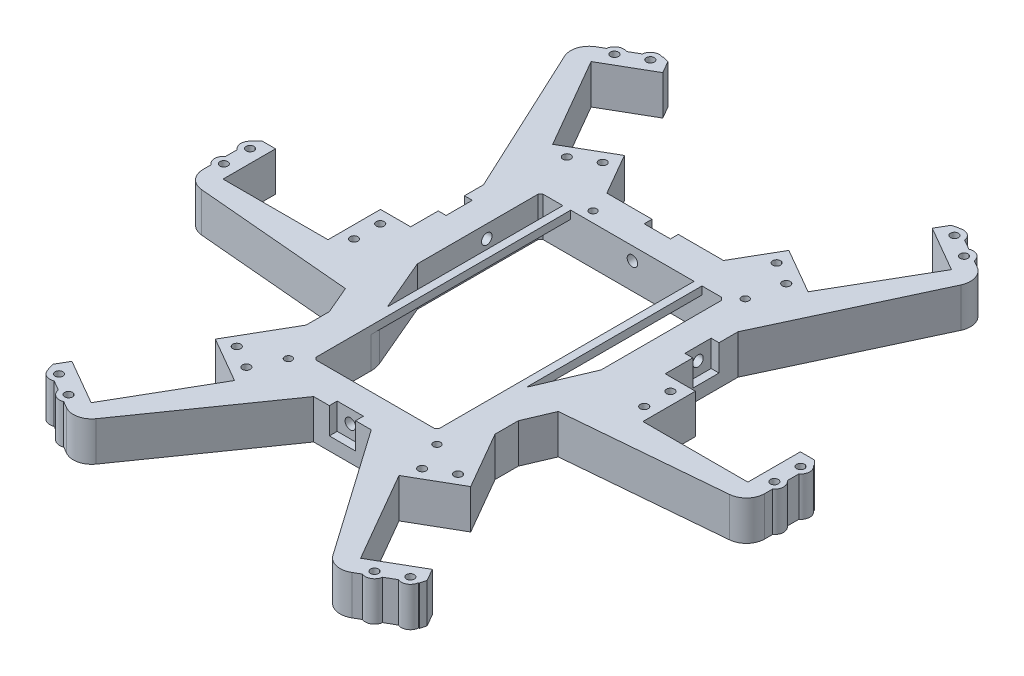
SolidWorks part; units mm, degrees
material "PETG"
ref_plane "Front Plane" through (0, 0, 0) normal (0, 0, 1) x (1, 0, 0)
ref_plane "Top Plane" through (0, 0, 0) normal (0, 1, 0) x (1, 0, 0)
ref_plane "Right Plane" through (0, 0, 0) normal (1, 0, 0) x (0, 0, -1)
sketch "Sketch1" plane through (0, 0, 0) normal (0, 1, 0) x (1, 0, 0)
  line L0 (-42.2601, -28.5633) -> (-31.2399, -54.4367)
  line L1 (-42.5, -28) -> (42.5, -28) construction
  line L2 (-42.5, -27.3877) -> (-42.5, 25)
  line L3 (-39.5, 28) -> (39.5, 28)
  line L4 (42.5, -27.3877) -> (42.5, 25)
  line L5 (-42.5, -28) -> (42.5, 28) construction
  line L6 (-42.5, 28) -> (42.5, -28) construction
  line L7 (-30, -85) -> (30, -85)
  line L8 (-31, -85) -> (-31, -43) construction
  line L9 (-31, -43) -> (31, -43) construction
  line L10 (31, -85) -> (31, -43) construction
  line L11 (-31, -85) -> (31, -43) construction
  line L12 (-31, -43) -> (31, -85) construction
  line L13 (-31, -55.6123) -> (-31, -84)
  line L14 (42.2601, -28.5633) -> (31.2399, -54.4367)
  line L15 (31, -55.6123) -> (31, -84)
  arc A0 (39.5, 28) -> (42.5, 25) centre (39.5, 25) cw
  arc A1 (-42.5, 25) -> (-39.5, 28) centre (-39.5, 25) cw
  arc A2 (-30, -85) -> (-31, -84) centre (-30, -84) cw
  arc A3 (30, -85) -> (31, -84) centre (30, -84) ccw
  arc A4 (-31.2399, -54.4367) -> (-31, -55.6123) centre (-34, -55.6123) cw
  arc A5 (31.2399, -54.4367) -> (31, -55.6123) centre (34, -55.6123) ccw
  arc A6 (42.2601, -28.5633) -> (42.5, -27.3877) centre (39.5, -27.3877) ccw
  arc A7 (-42.2601, -28.5633) -> (-42.5, -27.3877) centre (-39.5, -27.3877) cw
  point P0 (0, 0)
  point P12 (0, -64)
  point P31 (-31, -55)
  point P34 (31, -55)
  dimension "D3" = 3
  dimension "D8" = 1
  dimension "D9" = 3
  dimension "D1" = 85
  dimension "D2" = 56
  dimension "D4" = 62
  dimension "D5" = 42
  dimension "D6" = 15
  dimension "D7" = 30
extrude "Boss-Extrude1" add sketch "Sketch1" along normal blind 4
sketch "Sketch2" plane through (0, 4, 0) normal (0, 1, 0) x (1, 0, 0)
  line L0 (39.5, 28) -> (-39.5, 28) construction
  line L1 (42.5, -27.3877) -> (42.5, 25) construction
  line L2 (-31, -55.6123) -> (-31, -84) construction
  line L3 (-30, -85) -> (30, -85) construction
  line L5 (31, -84) -> (31, -55.6123) construction
  circle A0 centre (39, 24.5) radius 1.4
  circle A1 centre (-19, 24.5) radius 1.4
  circle A2 centre (-19, -24.5) radius 1.4
  circle A3 centre (39, -24.5) radius 1.4
  circle A4 centre (-28.3, -82.3) radius 1.4
  circle A5 centre (-28.3, -45.7) radius 1.4
  circle A6 centre (28.3, -45.7) radius 1.4
  circle A7 centre (28.3, -82.3) radius 1.4
  dimension "D3" = 2.8
  dimension "D4" = 2.8
  dimension "D5" = 2.8
  dimension "D6" = 2.8
  dimension "D9" = 2.8
  dimension "D14" = 2.8
  dimension "D15" = 2.8
  dimension "D16" = 2.8
  dimension "D12" = 2.7
  dimension "D1" = 3.5
  dimension "D2" = 3.5
  dimension "D7" = 49
  dimension "D8" = 58
  dimension "D10" = 2.7
  dimension "D11" = 2.7
  dimension "D13" = 36.6
sketch "Sketch11" plane through (0, 0, 0) normal (0, 1, 0) x (1, 0, 0)
  line L0 (0, -25.5) -> (-55, 69.7628) construction
  line L1 (0, -25.5) -> (-90, -25.5) construction
  line L2 (0, -25.5) -> (-55, -120.7628) construction
  line L3 (0, -25.5) -> (55, 69.7628) construction
  line L4 (0, -25.5) -> (90, -25.5) construction
  line L5 (0, -25.5) -> (55, -120.7628) construction
  line L6 (0, -18.7219) -> (0, 33) construction
  line L7 (48.6603, 38.782) -> (31.3397, 48.782)
  line L9 (41.7138, 26.7504) -> (25041.7138, 43328.0205) construction
  line L10 (24.3933, 36.7504) -> (25024.3933, 43338.0205) construction
  line L11 (48.6603, 38.782) -> (68.6603, 73.423)
  line L12 (68.6603, 73.423) -> (51.3397, 83.423)
  line L13 (51.3397, 83.423) -> (54.8397, 89.4852)
  line L14 (54.8397, 89.4852) -> (78.2224, 75.9852)
  line L16 (48.5, 12.2453) -> (48.5, -15.5)
  line L17 (60, -35.5) -> (100, -35.5)
  line L18 (100, -35.5) -> (100, -15.5)
  line L19 (100, -15.5) -> (107, -15.5)
  line L20 (107, -15.5) -> (107, -42.5)
  line L23 (41.5211, -131.4167) -> (-24958.4789, 43169.8535) construction
  line L24 (31.2399, -54.4367) -> (42.2601, -28.5633) construction
  line L32 (39, 33) -> (0, 33) construction
  line L33 (-48.5, 25) -> (-48.5, 24.5045) construction
  line L36 (0, -90) -> (28.3, -90) construction
  line L37 (36, -82.3) -> (36, -59) construction
  line L38 (36, -59) -> (46.7802, -33.6899) construction
  line L40 (35, 20.5) -> (-35, 20.5)
  line L41 (-35, 20.5) -> (-35, -26.4693)
  line L42 (-35, -26.4693) -> (-24.3397, -51.4977)
  line L43 (-23.5, -55.6123) -> (-23.5, -77.5)
  line L44 (-23.5, -77.5) -> (23.5, -77.5)
  line L45 (23.5, -77.5) -> (23.5, -55.6123)
  line L46 (24.3397, -51.4977) -> (35, -26.4693)
  line L47 (35, -26.4693) -> (35, 20.5)
  line L48 (35, 20.5) -> (-35, 20.5) construction
  line L49 (-35, 20.5) -> (-35, -26.4693) construction
  line L50 (-35, -26.4693) -> (-24.3397, -51.4977) construction
  line L51 (-23.5, -55.6123) -> (-23.5, -77.5) construction
  line L52 (-23.5, -77.5) -> (23.5, -77.5) construction
  line L53 (23.5, -77.5) -> (23.5, -55.6123) construction
  line L54 (24.3397, -51.4977) -> (35, -26.4693) construction
  line L55 (35, -26.4693) -> (35, 20.5) construction
  line L57 (48.7776, -143.9852) -> (72.1603, -130.4852)
  line L58 (72.1603, -130.4852) -> (68.6603, -124.423)
  line L59 (68.6603, -124.423) -> (51.3397, -134.423)
  line L60 (51.3397, -134.423) -> (31.3397, -99.782)
  line L61 (31.3397, -99.782) -> (48.6603, -89.782)
  line L63 (0, -90) -> (0, -77.5)
  line L64 (0, -77.5) -> (23.5, -77.5)
  line L65 (23.5, -77.5) -> (23.5, -55.6123)
  line L66 (0, 33) -> (0, 20.5)
  line L67 (0, 20.5) -> (35, 20.5)
  line L68 (35, 20.5) -> (35, -26.4693)
  line L69 (35, -26.4693) -> (24.3397, -51.4977)
  line L72 (40.5517, -48.3135) -> (107, -42.5)
  line L73 (78.2224, 75.9852) -> (-24921.7776, -43225.285) construction
  line L74 (78.2224, 75.9852) -> (48.5, 12.2453)
  line L75 (107, -42.5) -> (50107, -42.5) construction
  line L76 (48.7776, -143.9852) -> (10.9767, -90)
  line L82 (0, 44.3223) -> (0, 49981.2781) construction
  line L83 (31.3397, 48.782) -> (22.228, 33)
  line L84 (22.228, 33) -> (0, 33)
  line L85 (40.5517, -48.3135) -> (36, -59)
  line L86 (36, -59) -> (36, -67.8538)
  line L87 (36, -67.8538) -> (48.6603, -89.782)
  line L88 (10.9767, -90) -> (0, -90)
  line L89 (48.5, -15.5) -> (60, -15.5)
  line L90 (60, -15.5) -> (60, -35.5)
  line L92 (48.5, -15.5) -> (48.5, 12.2453) construction
  circle A0 centre (-28.3, -82.3) radius 1.4 construction
  circle A2 centre (-19, 24.5) radius 1.4 construction
  circle A4 centre (-28.3, -82.3) radius 1.4 construction
  circle A6 centre (-19, 24.5) radius 1.4 construction
  arc A22 (48.5, 23.5) -> (39, 33) centre (39, 23.5) ccw construction
  arc A26 (28.3, -90) -> (36, -82.3) centre (28.3, -82.3) ccw construction
  arc A27 (46.7802, -33.6899) -> (47.5, -30.1632) centre (38.5, -30.1632) ccw construction
  arc A28 (-23.5, -55.6123) -> (-24.3397, -51.4977) centre (-34, -55.6123) ccw
  arc A29 (24.3397, -51.4977) -> (23.5, -55.6123) centre (34, -55.6123) ccw
  arc A30 (-23.5, -55.6123) -> (-24.3397, -51.4977) centre (-34, -55.6123) ccw construction
  arc A31 (24.3397, -51.4977) -> (23.5, -55.6123) centre (34, -55.6123) ccw
  point P0 (0, -25.5)
  point P4 (33.775, 33)
  point P17 (-35.9261, -87.7258)
  point P27 (52.5, -25.5)
  point P28 (34.9923, -86.1084)
  point P30 (40, 43.782)
  point P31 (-33.775, 33)
  point P69 (34.9923, -86.1084)
  dimension "D28" = 40
  dimension "D1" = 60
  dimension "D2" = 60
  dimension "D3" = 60
  dimension "D4" = 33
  dimension "D6" = 46
  dimension "D7" = 5
  dimension "D8" = 5
  dimension "D9" = 40
  dimension "D10" = 7
  dimension "D11" = 27
  dimension "D12" = 20
  dimension "D13" = 10
  dimension "D14" = 10
  dimension "D15" = 7
  dimension "D16" = 10
  dimension "D17" = 7
  dimension "D18" = 10
  dimension "D19" = 14
  dimension "D20" = 7
  dimension "D21" = 10
  dimension "D22" = 40
  dimension "D23" = 5
  dimension "D24" = 10
  dimension "D25" = 110
  dimension "D26" = 90
  dimension "D27" = 10
  dimension "D29" = 25.5
  dimension "D30" = 48.5
  dimension "D31" = 36
  dimension "D32" = 64.5
  dimension "D33" = 31
  dimension "D5" = 7.5
extrude "Boss-Extrude4" add sketch "Sketch11" against normal blind 15
mirror "Mirror1" about plane through (0, 0, 0) normal (1, 0, 0) of "Boss-Extrude4"
sketch "Sketch14" plane through (0, 0, 0) normal (0, 1, 0) x (1, 0, 0)
  line L8 (39.5, 28) -> (-39.5, 28)
  line L9 (-42.5, 25) -> (-42.5, -27.3877)
  line L10 (-42.2601, -28.5633) -> (-31.2399, -54.4367)
  line L11 (-31, -55.6123) -> (-31, -84)
  line L12 (-30, -85) -> (30, -85)
  line L13 (31, -84) -> (31, -55.6123)
  line L14 (31.2399, -54.4367) -> (42.2601, -28.5633)
  line L15 (42.5, -27.3877) -> (42.5, 25)
  line L16 (39.5, 28) -> (-39.5, 28)
  line L17 (-42.5, 25) -> (-42.5, -27.3877)
  line L18 (-42.2601, -28.5633) -> (-31.2399, -54.4367)
  line L19 (-31, -55.6123) -> (-31, -84)
  line L20 (-30, -85) -> (30, -85)
  line L21 (31, -84) -> (31, -55.6123)
  line L22 (31.2399, -54.4367) -> (42.2601, -28.5633)
  line L23 (42.5, -27.3877) -> (42.5, 25)
  arc A8 (42.5, 25) -> (39.5, 28) centre (39.5, 25) ccw
  arc A9 (-39.5, 28) -> (-42.5, 25) centre (-39.5, 25) ccw
  arc A10 (-42.5, -27.3877) -> (-42.2601, -28.5633) centre (-39.5, -27.3877) ccw
  arc A11 (-31, -55.6123) -> (-31.2399, -54.4367) centre (-34, -55.6123) ccw
  arc A12 (-31, -84) -> (-30, -85) centre (-30, -84) ccw
  arc A13 (30, -85) -> (31, -84) centre (30, -84) ccw
  arc A14 (31.2399, -54.4367) -> (31, -55.6123) centre (34, -55.6123) ccw
  arc A15 (42.2601, -28.5633) -> (42.5, -27.3877) centre (39.5, -27.3877) ccw
  arc A16 (42.5, 25) -> (39.5, 28) centre (39.5, 25) ccw
  arc A17 (-39.5, 28) -> (-42.5, 25) centre (-39.5, 25) ccw
  arc A18 (-42.5, -27.3877) -> (-42.2601, -28.5633) centre (-39.5, -27.3877) ccw
  arc A19 (-31, -55.6123) -> (-31.2399, -54.4367) centre (-34, -55.6123) ccw
  arc A20 (-31, -84) -> (-30, -85) centre (-30, -84) ccw
  arc A21 (30, -85) -> (31, -84) centre (30, -84) ccw
  arc A22 (31.2399, -54.4367) -> (31, -55.6123) centre (34, -55.6123) ccw
  arc A23 (42.2601, -28.5633) -> (42.5, -27.3877) centre (39.5, -27.3877) ccw
  dimension "D1" = 0
extrude "Cut-Extrude5" cut sketch "Sketch14" along normal through all
sketch "Sketch15" plane through (0, 0, 0) normal (0, 1, 0) x (1, 0, 0)
  circle A0 centre (-28.3, -82.3) radius 1.4 construction
  circle A1 centre (28.3, -82.3) radius 1.4 construction
  circle A2 centre (-19, 24.5) radius 1.4 construction
  circle A3 centre (39, 24.5) radius 1.4 construction
  circle A4 centre (-28.3, -82.3) radius 1.4
  circle A5 centre (28.3, -82.3) radius 1.4
  circle A6 centre (-19, 24.5) radius 1.4
  circle A7 centre (39, 24.5) radius 1.4
extrude "Cut-Extrude6" cut sketch "Sketch15" against normal through all
chamfer "Chamfer1" distance 1 angle 45 4 edges at (35, -7.5, -20.5) (-35, -7.5, -20.5) (-23.5, -7.5, 77.5) (23.5, -7.5, 77.5)
sketch "Sketch16" plane through (0, 0, 0) normal (0, 1, 0) x (1, 0, 0)
  line L1 (26.5, 23.0975) -> (23.5, 23.0975)
  line L2 (26.5, 23.0975) -> (26.5, -77.5)
  line L3 (26.5, -77.5) -> (23.5, -77.5)
  line L4 (23.5, 23.0975) -> (23.5, -77.5)
  line L5 (26.5, 23.0975) -> (23.5, -77.5) construction
  line L6 (26.5, -77.5) -> (23.5, 23.0975) construction
  line L7 (22.5, -77.5) -> (-22.5, -77.5) construction
  point P0 (25, -27.2013)
  dimension "D1" = 3
extrude "Boss-Extrude7" add sketch "Sketch16" against normal blind 3
mirror "Mirror2" about plane through (0, 0, 0) normal (1, 0, 0) of "Boss-Extrude7"
sketch "Sketch17" plane through (0, 0, 0) normal (0, 1, 0) x (1, 0, 0)
  line L0 (22.228, 33) -> (-22.228, 33) construction
  line L1 (5, 33) -> (-5, 33)
  line L2 (5, 33) -> (5, 30)
  line L3 (5, 30) -> (-5, 30)
  line L4 (-5, 33) -> (-5, 30)
  line L5 (5, 33) -> (-5, 30) construction
  line L6 (5, 30) -> (-5, 33) construction
  line L7 (-48.5, -15.5) -> (-48.5, 12.2453) construction
  line L8 (-48.5, 5) -> (-45.5, 5)
  line L9 (-48.5, 5) -> (-48.5, -5)
  line L10 (-48.5, -5) -> (-45.5, -5)
  line L11 (-45.5, 5) -> (-45.5, -5)
  line L12 (-48.5, 5) -> (-45.5, -5) construction
  line L13 (-48.5, -5) -> (-45.5, 5) construction
  line L14 (48.5, -15.5) -> (48.5, 12.2453) construction
  line L15 (48.5, 5) -> (45.5, 5)
  line L16 (48.5, 5) -> (48.5, -5)
  line L17 (48.5, -5) -> (45.5, -5)
  line L18 (45.5, 5) -> (45.5, -5)
  line L19 (48.5, 5) -> (45.5, -5) construction
  line L20 (48.5, -5) -> (45.5, 5) construction
  line L21 (-10.9767, -90) -> (10.9767, -90) construction
  line L22 (5, -90) -> (-5, -90)
  line L23 (5, -90) -> (5, -87)
  line L24 (5, -87) -> (-5, -87)
  line L25 (-5, -90) -> (-5, -87)
  line L26 (5, -90) -> (-5, -87) construction
  line L27 (5, -87) -> (-5, -90) construction
  point P4 (0, 31.5)
  point P11 (-47, 0)
  point P18 (47, 0)
  point P25 (0, -88.5)
  dimension "D1" = 3
  dimension "D2" = 10
extrude "Cut-Extrude7" cut sketch "Sketch17" against normal blind 10
fillet "Fillet1" radius 7 6 edges at (107, -7.5, 42.5) (48.7776, -7.5, 143.9852) (-48.7776, -7.5, 143.9852) (-107, -7.5, 42.5) (78.2224, -7.5, -75.9852) (-78.2224, -7.5, -75.9852)
sketch "Sketch19" plane through (0, 0, -33) normal (0, 0, -1) x (-1, 0, 0)
  circle A0 centre (0, -5) radius 2
  dimension "D1" = 4
sketch "Sketch20" plane through (-48.5, 0, 0) normal (-1, 0, 0) x (0, 0, 1)
  circle A0 centre (0, -5) radius 2
  dimension "D1" = 4
sketch "Sketch21" plane through (0, 0, 90) normal (0, 0, 1) x (1, 0, 0)
  circle A0 centre (0, -5) radius 1.5 construction
extrude "Cut-Extrude10" cut sketch "Sketch19" against normal through all
extrude "Cut-Extrude11" cut sketch "Sketch20" against normal through all
ref_plane "Plane1" through (0, 0, 25.5) normal (0, 0, 1) x (1, 0, 0)
chamfer "Chamfer5" distance 1.7 angle 45 6 edges at (-107, -7.5, 15.5) (-72.1603, -7.5, 130.4852) (72.1603, -7.5, 130.4852) (107, -7.5, 15.5) (54.8397, -7.5, -89.4852) (-54.8397, -7.5, -89.4852)
sketch "Sketch25" plane through (0, 0, 0) normal (0, 1, 0) x (1, 0, 0)
  circle A0 centre (-28.3, -82.3) radius 3
  circle A1 centre (-19, 24.5) radius 3
  circle A2 centre (39, 24.5) radius 3
  circle A3 centre (28.3, -82.3) radius 3
  dimension "D1" = 6
sketch "Sketch26" plane through (0, -15, 0) normal (0, -1, 0) x (1, 0, 0)
  circle A0 centre (-19, -24.5) radius 3 construction
  circle A1 centre (39, -24.5) radius 3 construction
  circle A2 centre (28.3, 82.3) radius 3 construction
  circle A3 centre (-28.3, 82.3) radius 3 construction
  circle A4 centre (-19, -24.5) radius 3
  circle A5 centre (39, -24.5) radius 3
  circle A6 centre (28.3, 82.3) radius 3
  circle A7 centre (-28.3, 82.3) radius 3
extrude "Cut-Extrude14" cut sketch "Sketch26" against normal blind 6
chamfer "Chamfer7" distance 1.7 angle 45 4 edges at (-28.3, -9, 80.9) (28.3, -9, 80.9) (39, -9, -25.9) (-19, -9, -25.9)
sketch "Sketch28" plane through (0, -15, 0) normal (0, -1, 0) x (1, 0, 0)
  circle A0 centre (-41.8069, -37.3117) radius 1.5
  circle A1 centre (-33.1467, -42.3117) radius 1.5
  circle A2 centre (-66.6069, -80.2666) radius 1.5
  circle A3 centre (-57.9467, -85.2666) radius 1.5
  circle A4 centre (33.1467, -42.3117) radius 1.5
  circle A5 centre (41.8069, -37.3117) radius 1.5
  circle A6 centre (57.9467, -85.2666) radius 1.5
  circle A7 centre (66.6069, -80.2666) radius 1.5
  circle A8 centre (55.3, 20.3) radius 1.5
  circle A9 centre (55.3, 30.3) radius 1.5
  circle A10 centre (104.9, 20.3) radius 1.5
  circle A11 centre (104.9, 30.3) radius 1.5
  circle A12 centre (33.4931, 93.1117) radius 1.5
  circle A13 centre (42.1533, 88.1117) radius 1.5
  circle A14 centre (58.2931, 136.0666) radius 1.5
  circle A15 centre (66.9533, 131.0666) radius 1.5
  circle A16 centre (-66.9533, 131.0666) radius 1.5
  circle A17 centre (-58.2931, 136.0666) radius 1.5
  circle A18 centre (-42.1533, 88.1117) radius 1.5
  circle A19 centre (-33.4931, 93.1117) radius 1.5
  circle A20 centre (-104.9, 20.3) radius 1.5
  circle A21 centre (-104.9, 30.3) radius 1.5
  circle A22 centre (-55.3, 20.3) radius 1.5
  circle A23 centre (-55.3, 30.3) radius 1.5
  dimension "D1" = 3
extrude "Cut-Extrude15" cut sketch "Sketch28" against normal through all
sketch "Sketch29" plane through (0, -15, 0) normal (0, -1, 0) x (1, 0, 0)
  circle A0 centre (-66.6069, -80.2666) radius 3.5
  circle A1 centre (-57.9467, -85.2666) radius 3.5
  circle A2 centre (57.9467, -85.2666) radius 3.5
  circle A3 centre (66.6069, -80.2666) radius 3.5
  circle A4 centre (104.9, 30.3) radius 3.5
  circle A5 centre (104.9, 20.3) radius 3.5
  circle A6 centre (66.9533, 131.0666) radius 3.5
  circle A7 centre (58.2931, 136.0666) radius 3.5
  circle A8 centre (-66.9533, 131.0666) radius 3.5
  circle A9 centre (-58.2931, 136.0666) radius 3.5
  circle A10 centre (-104.9, 20.3) radius 3.5
  circle A11 centre (-104.9, 30.3) radius 3.5
  circle A12 centre (-104.9, 30.3) radius 1.5 construction
  circle A13 centre (-104.9, 20.3) radius 1.5 construction
  circle A14 centre (-58.2931, 136.0666) radius 1.5 construction
  circle A15 centre (-66.9533, 131.0666) radius 1.5 construction
  circle A16 centre (66.9533, 131.0666) radius 1.5 construction
  circle A17 centre (58.2931, 136.0666) radius 1.5 construction
  circle A18 centre (104.9, 30.3) radius 1.5 construction
  circle A19 centre (104.9, 20.3) radius 1.5 construction
  circle A20 centre (66.6069, -80.2666) radius 1.5 construction
  circle A21 centre (57.9467, -85.2666) radius 1.5 construction
  circle A22 centre (-57.9467, -85.2666) radius 1.5 construction
  circle A23 centre (-66.6069, -80.2666) radius 1.5 construction
  circle A24 centre (-104.9, 30.3) radius 1.5
  circle A25 centre (-104.9, 20.3) radius 1.5
  circle A26 centre (-58.2931, 136.0666) radius 1.5
  circle A27 centre (-66.9533, 131.0666) radius 1.5
  circle A28 centre (66.9533, 131.0666) radius 1.5
  circle A29 centre (58.2931, 136.0666) radius 1.5
  circle A30 centre (104.9, 30.3) radius 1.5
  circle A31 centre (104.9, 20.3) radius 1.5
  circle A32 centre (66.6069, -80.2666) radius 1.5
  circle A33 centre (57.9467, -85.2666) radius 1.5
  circle A34 centre (-57.9467, -85.2666) radius 1.5
  circle A35 centre (-66.6069, -80.2666) radius 1.5
  dimension "D1" = 7
extrude "Boss-Extrude8" add sketch "Sketch29" against normal up to surface (15 mm away) up to face at (33.4931, 0, 91.6117)
